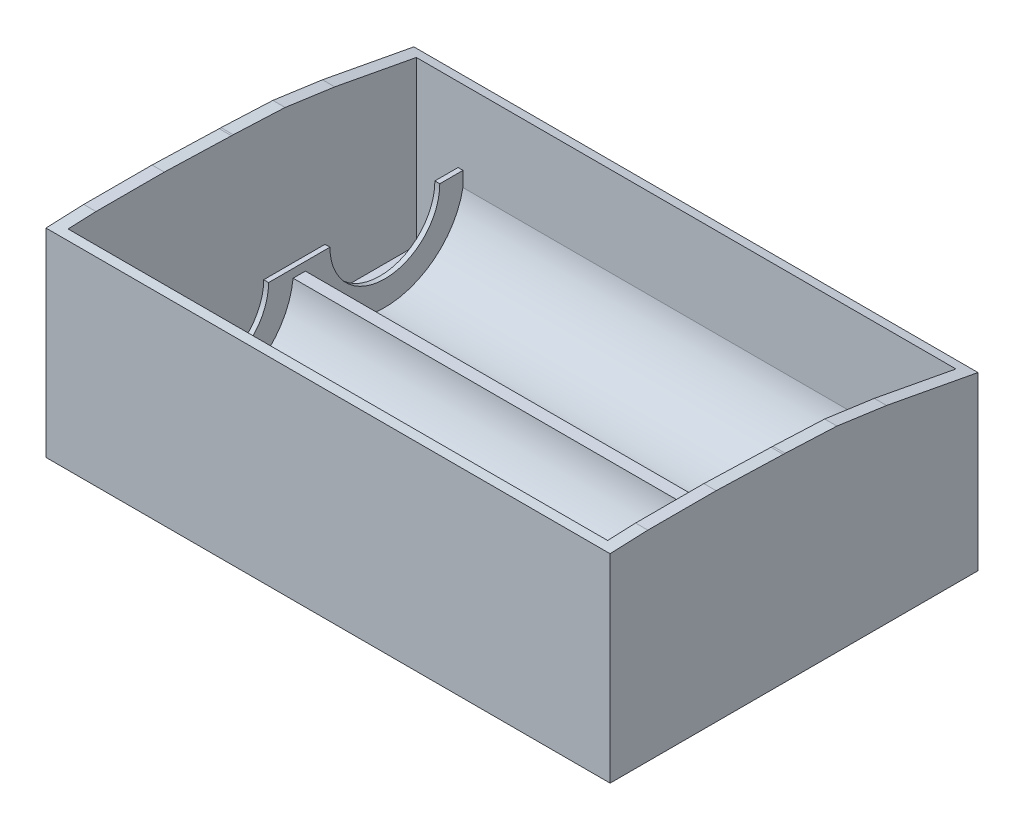
SolidWorks part; units mm, degrees
ref_plane "Front Plane" through (0, 0, 0) normal (0, 0, 1) x (1, 0, 0)
ref_plane "Top Plane" through (0, 0, 0) normal (0, 1, 0) x (1, 0, 0)
ref_plane "Right Plane" through (0, 0, 0) normal (1, 0, 0) x (0, 0, -1)
sketch "Sketch16" plane through (0, 0, 0) normal (1, 0, 0) x (0, 0, -1)
  line L0 (21.5465, 40.6394) -> (7.6186, 40.6394)
  line L1 (21.5465, 40.6394) -> (35.2383, 40.2055)
  line L2 (35.2383, 40.2055) -> (35.6026, 40.2055)
  line L3 (35.6026, 40.2055) -> (46.1712, 39.7312)
  line L4 (46.1712, 39.7312) -> (56.2876, 38.3122)
  line L5 (56.2876, 38.3122) -> (74.9264, 34.8087)
  line L6 (74.9264, 34.8087) -> (74.9264, -0.1913)
  line L7 (-0.0736, -0.1913) -> (74.9264, -0.1913)
  line L8 (-0.0736, -0.1913) -> (-0.0736, 40.3184)
  line L9 (-0.0736, 40.3184) -> (7.6186, 40.6394)
  dimension "D1" = 75
  dimension "D2" = 35
extrude "Boss-Extrude6" add sketch "Sketch16" along normal blind 115
sketch "Sketch17" plane through (0, 0, 0) normal (0, 1, 0) x (1, 0, 0)
  line L0 (0, 74.9264) -> (0, 56.2876) construction
  line L1 (2.5, 72.9264) -> (112.5, 72.9264)
  line L2 (2.5, 72.9264) -> (2.5, 1.9264)
  line L3 (2.5, 1.9264) -> (112.5, 1.9264)
  line L4 (112.5, 72.9264) -> (112.5, 1.9264)
  line L8 (115, 74.9264) -> (0, 74.9264) construction
  dimension "D1" = 110
  dimension "D2" = 2.5
  dimension "D3" = 71
  dimension "D4" = 2
extrude "Cut-Extrude5" cut sketch "Sketch17" along normal blind 115 from offset 2
sketch "Sketch18" plane through (0, 2, 0) normal (0, 1, 0) x (1, 0, 0)
  line L0 (0, 56.2876) -> (0, 46.1712) construction
  line L1 (12, 71.4264) -> (103, 71.4264)
  line L2 (12, 71.4264) -> (12, 3.4264)
  line L3 (12, 3.4264) -> (103, 3.4264)
  line L4 (103, 71.4264) -> (103, 3.4264)
  line L5 (112.5, 72.9264) -> (2.5, 72.9264) construction
  dimension "D1" = 91
  dimension "D2" = 12
  dimension "D3" = 68
  dimension "D4" = 1.5
sketch "Sketch21" plane through (0, 0, 0) normal (-1, 0, 0) x (0, 0, 1)
  line L0 (-73.213, 2) -> (-73.213, 20)
  line L1 (-5.8972, 2) -> (-5.8972, 20)
  line L2 (-40.8051, 18.2725) -> (-38.3051, 18.2725)
  line L3 (-71.4264, 2) -> (-3.4264, 2) construction
  line L4 (-73.213, 2) -> (-5.8972, 2)
  arc A0 (-73.213, 20) -> (-40.8051, 18.2725) centre (-56.963, 20) ccw
  arc A1 (-5.8972, 20) -> (-38.3051, 18.2725) centre (-22.1472, 20) cw
  dimension "D2" = 16.25
  dimension "D3" = 16.25
  dimension "D4" = 18
  dimension "D1" = 2.5
  dimension "D5" = 18
extrude "Boss-Extrude7" add sketch "Sketch21" against normal up to vertex (103 mm away) from vertex up to point (103, 2, -71.4264) starting at point (12, 2, -71.4264)
sketch "Sketch22" plane through (0, 2, 0) normal (0, 1, 0) x (1, 0, 0)
  line L0 (12, 5.8972) -> (12, 1.9264)
  line L1 (2.5, 1.9264) -> (112.5, 1.9264) construction
  line L2 (12, 1.9264) -> (103, 1.9264)
  line L3 (2.5, 1.9264) -> (112.5, 1.9264) construction
  line L4 (103, 1.9264) -> (103, 5.8972)
  line L5 (103, 5.8972) -> (12, 5.8972)
  line L7 (12, 72.9264) -> (2.5, 72.9264) construction
  line L8 (2.5, 72.9264) -> (2.5, 1.9264) construction
  line L9 (112.5, 1.9264) -> (112.5, 7.6186) construction
  circle A0 centre (7, 69.4264) radius 2.75
  circle A1 centre (108, 69.4264) radius 2.75
  circle A2 centre (108, 5.4264) radius 2.75
  circle A3 centre (7, 5.4264) radius 2.75
  point P24 (0, 0)
  dimension "D5" = 5.5
  dimension "D1" = 3.5
  dimension "D2" = 3.5
  dimension "D3" = 4.5
  dimension "D4" = 4.5
extrude "Cut-Extrude6" cut sketch "Sketch22" against normal through all
sketch "Sketch23" plane through (0, 0, 0) normal (-1, 0, 0) x (0, 0, 1)
  line L0 (-73.213, 20) -> (-5.8972, 20)
  line L1 (-5.8972, 20) -> (-5.8972, 2)
  line L2 (-5.8972, 2) -> (-73.213, 2)
  line L3 (-73.213, 2) -> (-73.213, 20)
extrude "Boss-Extrude8" add sketch "Sketch23" along normal blind 1 from surface starting at face at (12, 8.0483, -39.2288)
sketch "Sketch24" plane through (115, 0, 0) normal (1, 0, 0) x (0, 0, -1)
  line L0 (5.8972, 20) -> (73.213, 20)
  line L1 (73.213, 20) -> (73.213, 2)
  line L2 (73.213, 2) -> (5.8972, 2)
  line L3 (5.8972, 2) -> (5.8972, 20)
extrude "Boss-Extrude9" add sketch "Sketch24" along normal blind 1 from surface starting at face at (103, 8.0483, -39.2288)
sketch "Sketch25" plane through (11, 0, 0) normal (-1, 0, 0) x (0, 0, 1)
  line L6 (-68.2051, 20) -> (-45.8051, 20)
  line L7 (-33.3051, 20) -> (-10.9051, 20)
  arc A0 (-68.2051, 20) -> (-45.8051, 20) centre (-57.0051, 20) ccw
  arc A1 (-33.3051, 20) -> (-10.9051, 20) centre (-22.1051, 20) ccw
  dimension "D1" = 11.2
  dimension "D2" = 11.2
  dimension "D3" = 5
  dimension "D4" = 5
extrude "Cut-Extrude7" cut sketch "Sketch25" against normal up to surface (1 mm away) up to face at (12, 12.858, -45.8952)
sketch "Sketch26" plane through (104, 0, 0) normal (1, 0, 0) x (0, 0, -1)
  line L10 (10.9051, 20) -> (33.3051, 20)
  line L11 (45.8051, 20) -> (68.2051, 20)
  arc A2 (10.9051, 20) -> (33.3051, 20) centre (22.1051, 20) ccw
  arc A3 (45.8051, 20) -> (68.2051, 20) centre (57.0051, 20) ccw
  dimension "D1" = 11.2
  dimension "D4" = 11.2
extrude "Cut-Extrude8" cut sketch "Sketch26" against normal up to surface (1 mm away) up to face at (103, 12.858, -45.8952)
